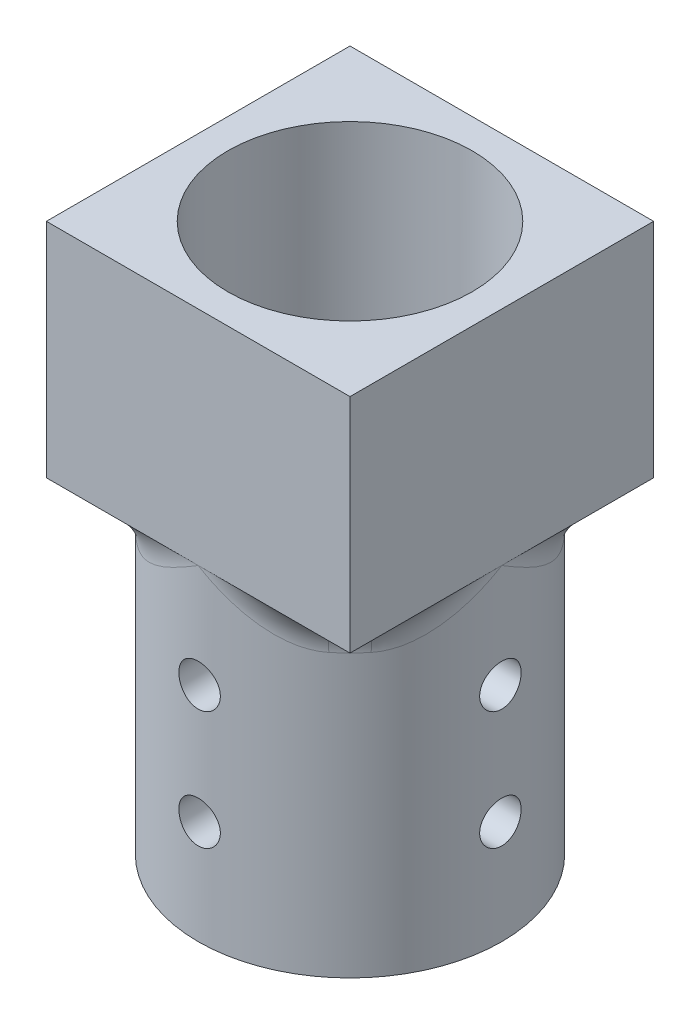
SolidWorks part; units mm, degrees
ref_plane "Front Plane" through (0, 0, 0) normal (0, 0, 1) x (1, 0, 0)
ref_plane "Top Plane" through (0, 0, 0) normal (0, 1, 0) x (1, 0, 0)
ref_plane "Right Plane" through (0, 0, 0) normal (1, 0, 0) x (0, 0, -1)
sketch "Sketch1" plane through (0, 0, 0) normal (0, 1, 0) x (1, 0, 0)
  circle A0 centre (0, 0) radius 8.25
  circle A1 centre (0, 0) radius 10.25
  dimension "D1" = 16.5
  dimension "D2" = 2
extrude "Boss-Extrude1" add sketch "Sketch1" along normal blind 25
sketch "Sketch2" plane through (0, 0, 0) normal (0, 0, 1) x (1, 0, 0)
  circle A0 centre (0, 13) radius 1.4 construction
  circle A1 centre (0, 13) radius 1.4
  circle A2 centre (0, 5) radius 1.4 construction
  circle A3 centre (0, 5) radius 1.4
extrude "Cut-Extrude1" cut sketch "Sketch2" against normal through all and the other way through all
pattern_circular "CirPattern1" count 2 over 90 about axis through (0, 25, 0) along (0, -1, 0) of "Cut-Extrude1"
sketch "Sketch3" plane through (0, 0, 0) normal (0, -1, 0) x (1, 0, 0)
  circle A0 centre (0, 0) radius 6.9
  circle A1 centre (0, 0) radius 10.25
  circle A2 centre (0, 0) radius 10.25
  dimension "D1" = 0
extrude "Boss-Extrude2" add sketch "Sketch3" along normal blind 2
sketch "Sketch4" plane through (0, 25, 0) normal (0, 1, 0) x (1, 0, 0)
  line L1 (-10.25, 10.25) -> (10.25, 10.25)
  line L2 (-10.25, 10.25) -> (-10.25, -10.25)
  line L3 (-10.25, -10.25) -> (10.25, -10.25)
  line L4 (10.25, 10.25) -> (10.25, -10.25)
  circle A0 centre (0, 0) radius 10.25 construction
  circle A1 centre (0, 0) radius 8.25 construction
  circle A2 centre (0, 0) radius 8.25
extrude "Boss-Extrude3" add sketch "Sketch4" along normal blind 10 and the other way blind 5
fillet "Fillet1" radius 3 4 edges at (7.2478, 20, 7.2478) (-7.2478, 20, 7.2478) (-7.2478, 20, -7.2478) (7.2478, 20, -7.2478)
